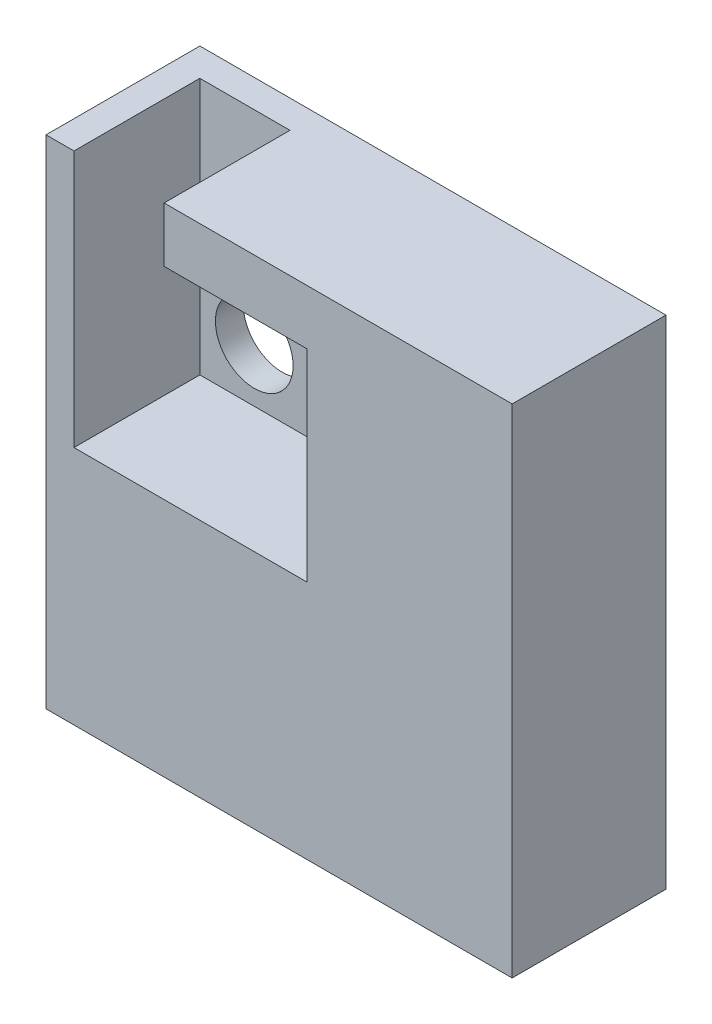
SolidWorks part; units mm, degrees
ref_plane "Front Plane" through (0, 0, 0) normal (0, 0, 1) x (1, 0, 0)
ref_plane "Top Plane" through (0, 0, 0) normal (0, 1, 0) x (1, 0, 0)
ref_plane "Right Plane" through (0, 0, 0) normal (1, 0, 0) x (0, 0, -1)
sketch "Sketch1" plane through (0, 0, 0) normal (0, 0, 1) x (1, 0, 0)
  line L1 (0, 0) -> (30, 0)
  line L2 (0, 0) -> (0, 32)
  line L3 (0, 32) -> (30, 32)
  line L4 (30, 0) -> (30, 32)
  dimension "D1" = 30
  dimension "D2" = 32
extrude "Boss-Extrude1" add sketch "Sketch1" along normal blind 9.9
sketch "Sketch2" plane through (0, 0, 9.9) normal (0, 0, 1) x (1, 0, 0)
  line L0 (0, 32) -> (0, 0) construction
  line L1 (7.6, 32) -> (7.6, 28.4669)
  line L2 (7.6, 28.4669) -> (16.8, 28.4669)
  line L4 (1.8, 28.4669) -> (1.8, 15.4669)
  line L5 (1.8, 15.4669) -> (16.8, 15.4669)
  line L6 (16.8, 28.4669) -> (16.8, 15.4669)
  line L7 (1.8, 28.4669) -> (1.8, 32)
  line L8 (30, 32) -> (0, 32) construction
  line L9 (1.8, 32) -> (7.6, 32)
  dimension "D1" = 15
  dimension "D2" = 13
  dimension "D3" = 1.8
  dimension "D4" = 5.8
extrude "Cut-Extrude1" cut sketch "Sketch2" against normal blind 8.1
sketch "Sketch3" plane through (0, 0, 1.8) normal (0, 0, 1) x (1, 0, 0)
  line L0 (1.8, 32) -> (1.8, 15.4669) construction
  line L1 (1.8, 15.4669) -> (16.8, 15.4669) construction
  circle A0 centre (5.3, 18.9669) radius 2.5
  dimension "D2" = 3.5
  dimension "D3" = 5
  dimension "D1" = 3.5
extrude "Cut-Extrude2" cut sketch "Sketch3" against normal through all
